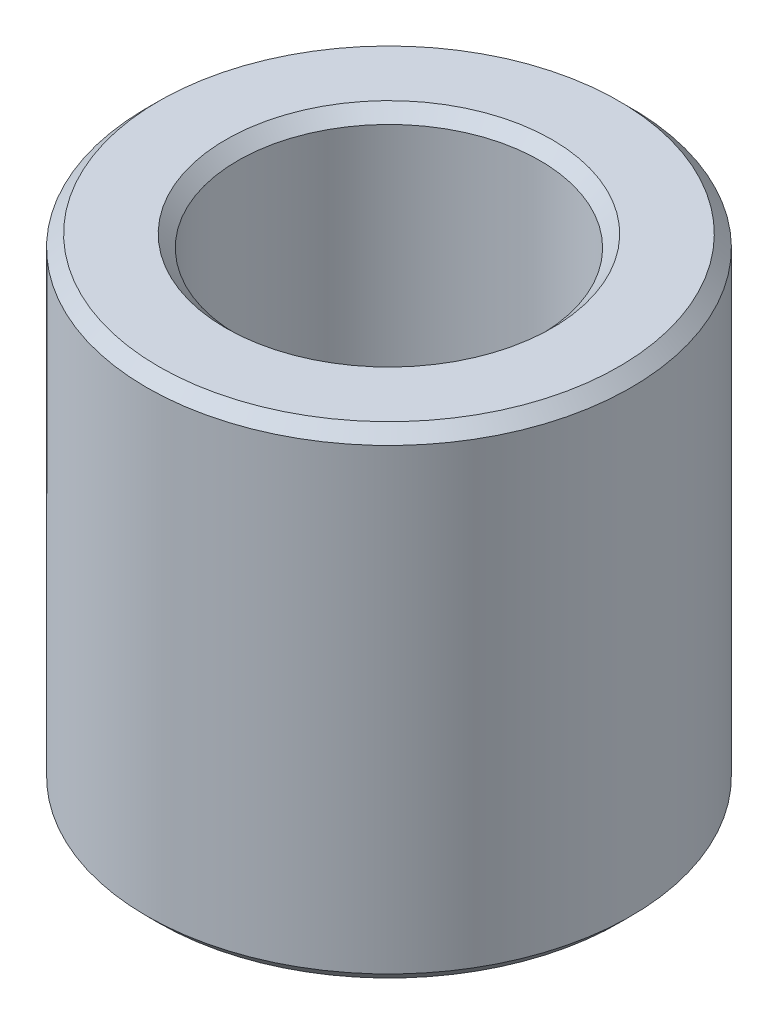
SolidWorks part; units mm, degrees
ref_plane "Front Plane" through (0, 0, 0) normal (0, 0, 1) x (1, 0, 0)
ref_plane "Top Plane" through (0, 0, 0) normal (0, 1, 0) x (1, 0, 0)
ref_plane "Right Plane" through (0, 0, 0) normal (1, 0, 0) x (0, 0, -1)
sketch "Sketch1" plane through (0, 0, 0) normal (0, 1, 0) x (1, 0, 0)
  circle A0 centre (0, 0) radius 57.5
  dimension "SLEEVE_OD" = 115
extrude "Boss-Extrude1" add sketch "Sketch1" along normal blind 114.4161
sketch "Sketch2" plane through (0, 0, 0) normal (0, 1, 0) x (1, 0, 0)
  circle A0 centre (0, 0) radius 35.8812
  dimension "BORE_D" = 71.7623
extrude "Cut-Extrude1" cut sketch "Sketch2" along normal through all
chamfer "Chamfer1" distance 2.8676 angle 45 4 edges at (0, 114.4161, 35.8812) (0, 0, 35.8812) (0, 0, 57.5) (0, 114.4161, 57.5)
